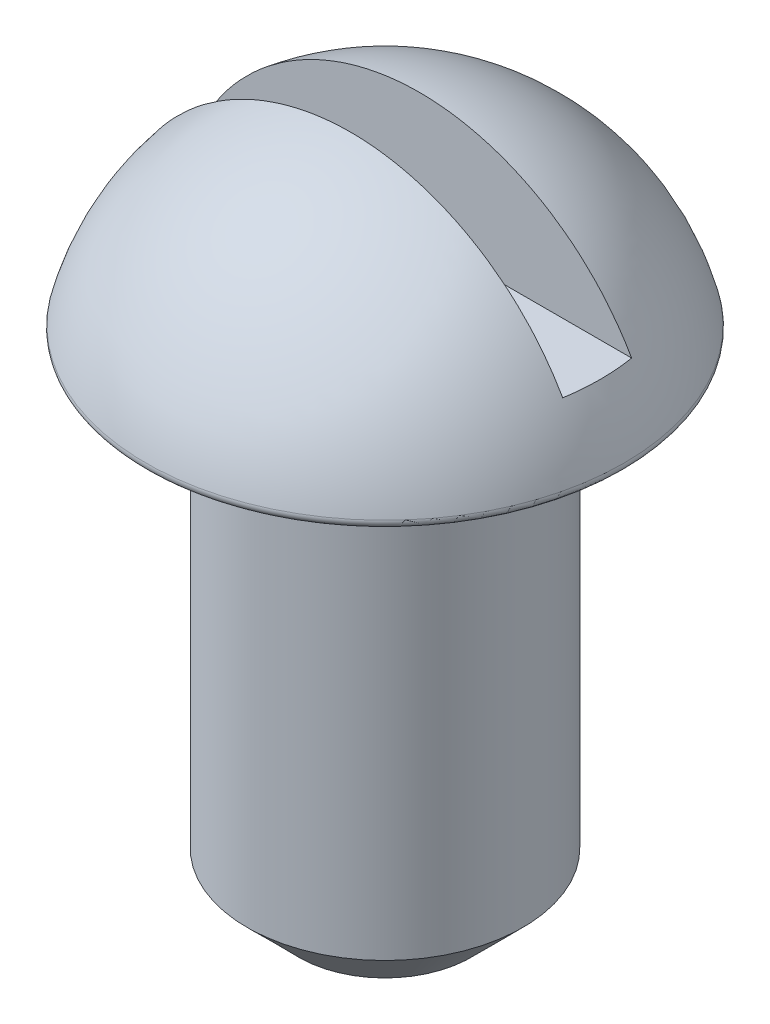
SolidWorks part; units mm, degrees
ref_plane "Спереди" through (0, 0, 0) normal (0, 0, 1) x (1, 0, 0)
ref_plane "Сверху" through (0, 0, 0) normal (0, 1, 0) x (1, 0, 0)
ref_plane "Справа" through (0, 0, 0) normal (1, 0, 0) x (0, 0, -1)
sketch "Эскиз1" plane through (0, 0, 0) normal (0, 0, 1) x (1, 0, 0)
  line L0 (0, 125.7632) -> (0, 0) construction
  line L1 (2, 91.4493) -> (3.5, 91.4493)
  line L2 (0, 94.2493) -> (0, 84.2493)
  line L3 (0, 94.2493) -> (0.5, 94.2493)
  line L4 (2, 91.4493) -> (2, 84.2493)
  line L6 (2, 84.2493) -> (0, 84.2493)
  arc A0 (0.5, 94.2493) -> (3.5, 91.4493) centre (-0.0183, 90.6868) cw
  dimension "D1" = 0.5
  dimension "D2" = 2.8
  dimension "D3" = 10
  dimension "D4" = 3.6
  dimension "D5" = 2
  dimension "D6" = 3.5
revolve "Повернуть1" add sketch "Эскиз1" angle 360 about L0
ref_axis "Ось4" through (0, 0.4667, 0) along (0, -1, 0)
sketch "Эскиз13" plane through (0, 94.2493, 0) normal (0, 1, 0) x (-1, 0, 0)
  line L1 (3.5, -0.5) -> (-3.5, -0.5)
  line L2 (3.5, -0.5) -> (3.5, 0.5)
  line L3 (3.5, 0.5) -> (-3.5, 0.5)
  line L4 (-3.5, -0.5) -> (-3.5, 0.5)
  dimension "D1" = 3.5
  dimension "D2" = 7
  dimension "D3" = 0.5
  dimension "D4" = 1
extrude "Вырез-Вытянуть9" cut sketch "Эскиз13" against normal blind 1.8
fillet "Скругление1" radius 0.1 1 edges at (-3.5, 91.4493, 0)
chamfer "Фаска1" distance 0.75 angle 45 1 edges at (-2, 84.2493, 0)
